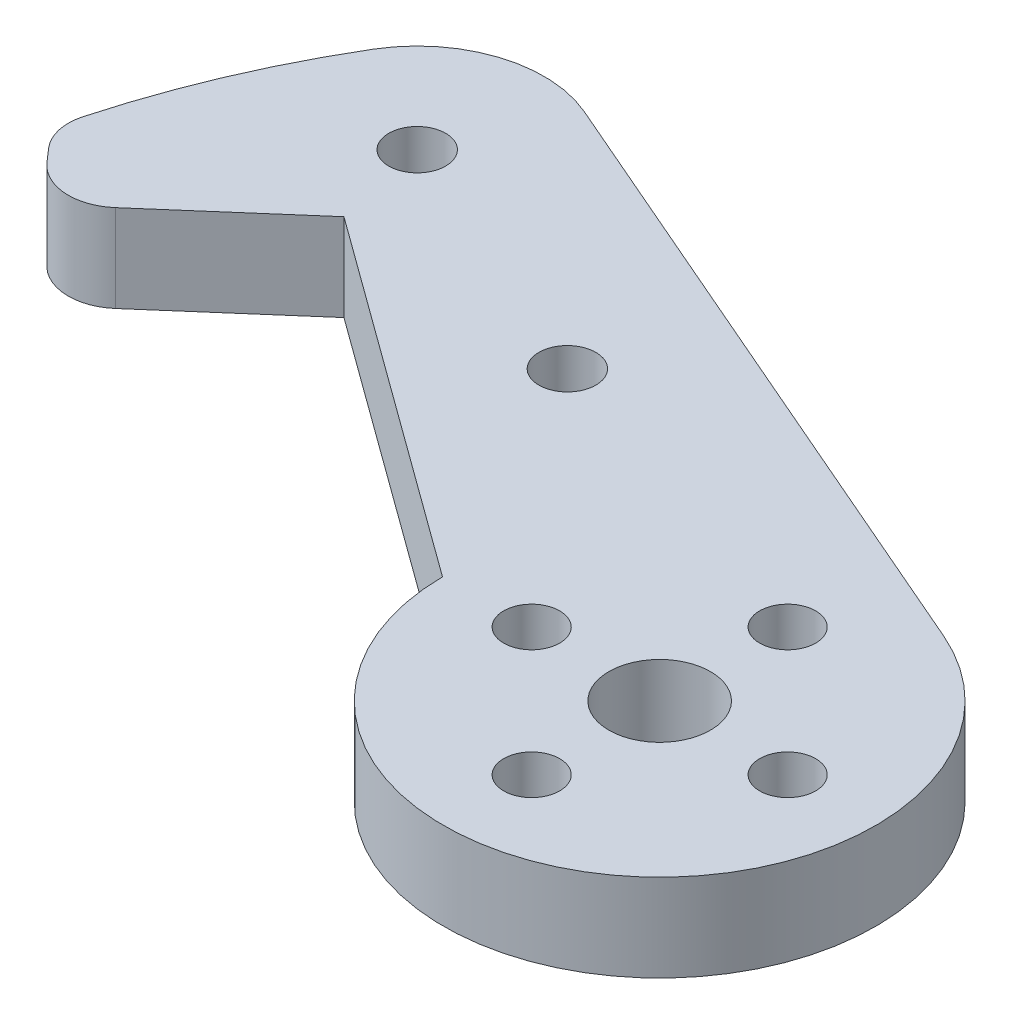
SolidWorks part; units mm, degrees
ref_plane "Front" through (0, 0, 0) normal (0, 0, 1) x (1, 0, 0)
ref_plane "Top" through (0, 0, 0) normal (0, 1, 0) x (1, 0, 0)
ref_plane "Right" through (0, 0, 0) normal (1, 0, 0) x (0, 0, -1)
ref_axis "side-side" through (80.9, 0, 0) along (-1, 0, 0)
ref_axis "up-down" through (0, 50, 0) along (0, -1, 0)
ref_axis "front-back" through (0, 0, -80.9) along (0, 0, 1)
sketch "Sketch1" plane through (0, 0, 0) normal (0, 1, 0) x (1, 0, 0)
  line L0 (-43.7133, 9.6871) -> (-36.0756, 16.3422) construction
  line L1 (-36.0756, 16.3422) -> (-43.7133, 9.6871)
  line L2 (-36.0756, 16.3422) -> (-13.4998, -0.0747)
  line L3 (-48.2987, 10.0023) -> (-49.0144, 10.8238)
  line L4 (-32.187, 16.1021) -> (-45.5823, 21.8655) construction
  line L5 (-34.2596, 29.5434) -> (5.3636, 12.3888)
  arc A0 (-43.7133, 9.6871) -> (-48.2987, 10.0023) centre (-45.8484, 12.1374) cw
  arc A1 (-49.6462, 13.5865) -> (-44.2347, 26.3178) centre (0, 0) cw
  arc A2 (-49.6462, 13.5865) -> (-49.0144, 10.8238) centre (-46.7526, 12.7946) ccw
  arc A3 (-34.2596, 29.5434) -> (-44.2347, 26.3178) centre (-37.4133, 22.2593) ccw
  arc A4 (-48.2987, 10.0023) -> (-43.7133, 9.6871) centre (-45.8484, 12.1374) ccw construction
  arc A5 (-13.4998, -0.0747) -> (5.3636, 12.3888) centre (0, 0) ccw
  circle A6 centre (8, 0) radius 1.75 construction
  circle A7 centre (0, -8) radius 1.75 construction
  circle A8 centre (-8, 0) radius 1.75 construction
  circle A9 centre (0, 8) radius 1.75 construction
  circle A10 centre (8, 0) radius 1.75
  circle A11 centre (0, -8) radius 1.75
  circle A12 centre (-8, 0) radius 1.75
  circle A13 centre (0, 8) radius 1.75
  circle A14 centre (-37.6448, 21.8655) radius 7.9375 construction
  circle A15 centre (0, 0) radius 3.175
  circle A16 centre (-20.8625, 15.0937) radius 7.9375 construction
  circle A17 centre (-20.8625, 15.0937) radius 1.778
  circle A18 centre (-37.4133, 22.2593) radius 1.778
  arc A21 (-49.6462, 13.5865) -> (-49.0144, 10.8238) centre (-46.7526, 12.7946) ccw construction
  point P0 (-37.4529, 17.3438)
  point P44 (0, 0)
  point P47 (0, 0)
  point P49 (0, 0)
  dimension "D2" = 3
  dimension "D4" = 27
  dimension "D5" = 51.4717
  dimension "D8" = 3.25
  dimension "D11" = 15.875
  dimension "D13" = 6.35
  dimension "D14" = 3.556
  dimension "D1" = 13
  dimension "D3" = 8
  dimension "D6" = 102.908
  dimension "D10" = 12.4641
  dimension "D12" = 25.75
extrude "Boss-Extrude1" add sketch "Sketch1" along normal blind 5.461
